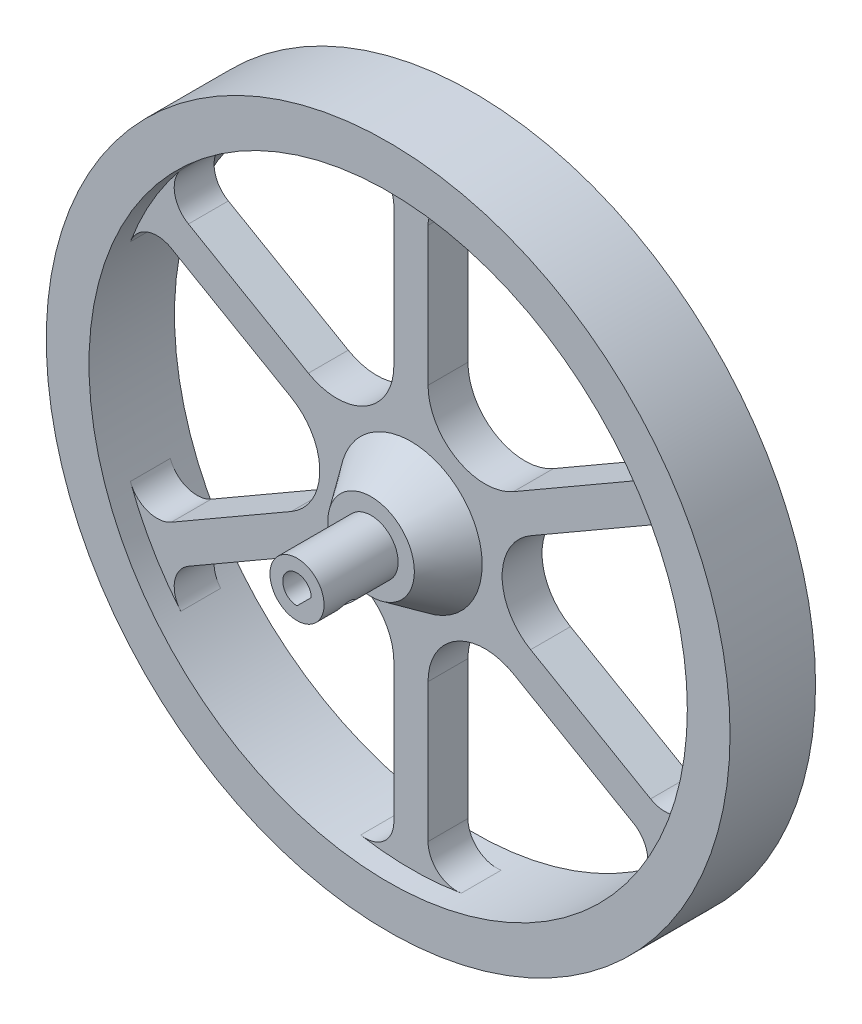
SolidWorks part; units mm, degrees
other "Marca1"
sketch "Croquis9" plane through (60, -60, 20.5) normal (0.1284, -0.1342, 0.9826) x (0.6376, -0.7477, -0.1854)
ref_plane "Alzado" through (0, 0, 0) normal (0, 0, 1) x (1, 0, 0)
ref_plane "Planta" through (0, 0, 0) normal (0, 1, 0) x (1, 0, 0)
ref_plane "Vista lateral" through (0, 0, 0) normal (1, 0, 0) x (0, 0, -1)
sketch "Croquis1" plane through (0, 0, 0) normal (0, 0, 1) x (1, 0, 0)
  circle A0 centre (0, 0) radius 60
  dimension "D1" = 120
extrude "Saliente-Extruir1" add sketch "Croquis1" along normal mid plane 15
sketch "Croquis2" plane through (0, 0, 7.5) normal (0, 0, 1) x (1, 0, 0)
  circle A0 centre (0, 0) radius 52.5
  dimension "D1" = 105
extrude "Cortar-Extruir1" cut sketch "Croquis2" against normal blind 4
mirror "Simetría1" about plane through (0, 0, 0) normal (0, 0, 1) of "Cortar-Extruir1"
sketch "Croquis4" plane through (0, 0, 3.5) normal (0, 0, 1) x (1, 0, 0)
  circle A0 centre (0, 0) radius 4.75
  dimension "D1" = 9.5
extrude "Saliente-Extruir2" add sketch "Croquis4" along normal blind 20
sketch "Croquis6" plane through (0, 0, 3.5) normal (0, 0, 1) x (1, 0, 0)
  circle A0 centre (0, 0) radius 12.5
  dimension "D1" = 25
extrude "Saliente-Extruir3" add sketch "Croquis6" along normal blind 7 draft 35
sketch "Croquis5" plane through (0, 0, 23.5) normal (0, 0, 1) x (1, 0, 0)
  line L0 (2.5, 0) -> (0, -2.5)
  arc A0 (2.5, 0) -> (0, -2.5) centre (0, 0) ccw
  dimension "D1" = 5
extrude "Cortar-Extruir3" cut sketch "Croquis5" against normal blind 20
sketch "Croquis7" plane through (1.25, -1.25, 0) normal (-0.7071, 0.7071, 0) x (0, 0, 1)
  line L0 (23.5, -1.7678) -> (23.5, 1.7678) construction
  circle A0 centre (18.5, 0) radius 1.5
  dimension "D1" = 3
  dimension "D2" = 5
extrude "Cortar-Extruir4" cut sketch "Croquis7" against normal up to next
sketch "Croquis8" plane through (0, 0, 3.5) normal (0, 0, 1) x (1, 0, 0)
  line L0 (0, 0) -> (72.0449, 41.5952) construction
  line L1 (0, 0) -> (0, 60) construction
  line L3 (3, 46.8215) -> (3, 22.5167)
  line L4 (0, 0) -> (26.25, 45.4663) construction
  line L15 (39.0486, 26.0088) -> (18, 13.8564)
  line L26 (42.0486, -20.8127) -> (21, -8.6603)
  line L27 (42.0486, 20.8127) -> (21, 8.6603)
  line L28 (3, -46.8215) -> (3, -22.5167)
  line L29 (39.0486, -26.0088) -> (18, -13.8564)
  line L30 (-39.0486, -26.0088) -> (-18, -13.8564)
  line L31 (-3, -46.8215) -> (-3, -22.5167)
  line L32 (-42.0486, 20.8127) -> (-21, 8.6603)
  line L33 (-42.0486, -20.8127) -> (-21, -8.6603)
  line L34 (-3, 46.8215) -> (-3, 22.5167)
  line L35 (-39.0486, 26.0088) -> (-18, 13.8564)
  circle A2 centre (0, 0) radius 60 construction
  circle A3 centre (0, 0) radius 52.5 construction
  arc A5 (3, 22.5167) -> (18, 13.8564) centre (13, 22.5167) ccw
  arc A31 (40.3958, 33.5325) -> (8.8421, 51.75) centre (0, 0) ccw
  arc A32 (39.0486, 26.0088) -> (40.3958, 33.5325) centre (36.5486, 30.3389) ccw
  arc A33 (3, 46.8215) -> (8.8421, 51.75) centre (8, 46.8215) cw
  arc A34 (42.0486, -20.8127) -> (49.2379, -18.2175) centre (44.5486, -16.4825) ccw
  arc A35 (49.2379, -18.2175) -> (49.2379, 18.2175) centre (0, 0) ccw
  arc A36 (42.0486, 20.8127) -> (49.2379, 18.2175) centre (44.5486, 16.4825) cw
  arc A37 (21, 8.6603) -> (21, -8.6603) centre (26, 0) ccw
  arc A38 (3, -46.8215) -> (8.8421, -51.75) centre (8, -46.8215) ccw
  arc A39 (8.8421, -51.75) -> (40.3958, -33.5325) centre (0, 0) ccw
  arc A40 (39.0486, -26.0088) -> (40.3958, -33.5325) centre (36.5486, -30.3389) cw
  arc A41 (18, -13.8564) -> (3, -22.5167) centre (13, -22.5167) ccw
  arc A42 (-39.0486, -26.0088) -> (-40.3958, -33.5325) centre (-36.5486, -30.3389) ccw
  arc A43 (-40.3958, -33.5325) -> (-8.8421, -51.75) centre (0, 0) ccw
  arc A44 (-3, -46.8215) -> (-8.8421, -51.75) centre (-8, -46.8215) cw
  arc A45 (-3, -22.5167) -> (-18, -13.8564) centre (-13, -22.5167) ccw
  arc A46 (-42.0486, 20.8127) -> (-49.2379, 18.2175) centre (-44.5486, 16.4825) ccw
  arc A47 (-49.2379, 18.2175) -> (-49.2379, -18.2175) centre (0, 0) ccw
  arc A48 (-42.0486, -20.8127) -> (-49.2379, -18.2175) centre (-44.5486, -16.4825) cw
  arc A49 (-21, -8.6603) -> (-21, 8.6603) centre (-26, 0) ccw
  arc A50 (-3, 46.8215) -> (-8.8421, 51.75) centre (-8, 46.8215) ccw
  arc A51 (-8.8421, 51.75) -> (-40.3958, 33.5325) centre (0, 0) ccw
  arc A52 (-39.0486, 26.0088) -> (-40.3958, 33.5325) centre (-36.5486, 30.3389) cw
  arc A53 (-18, 13.8564) -> (-3, 22.5167) centre (-13, 22.5167) ccw
  point P14 (43.892, 28.8052)
  point P17 (3, 52.4142)
  point P63 (0, 0)
  point P69 (0, 0)
  point P72 (0, 0)
  dimension "D2" = 3
  dimension "D3" = 10
  dimension "D4" = 5
  dimension "D1" = 60
  dimension "D5" = 6
  dimension "D6" = 30
extrude "Cortar-Extruir5" cut sketch "Croquis8" against normal up to next
sketch "Croquis10" plane through (0, 0, -3.5) normal (0, 0, -1) x (-1, 0, 0)
  line L0 (-10.2533, -5) -> (10.2533, -5) construction
  line L1 (0, 0) -> (0, -5) construction
  text T0 "2GD" font "Century Schoolbook" height in points 28
  dimension "D1" = 5
extrude "Cortar-Extruir6" cut sketch "Croquis10" against normal blind 3
